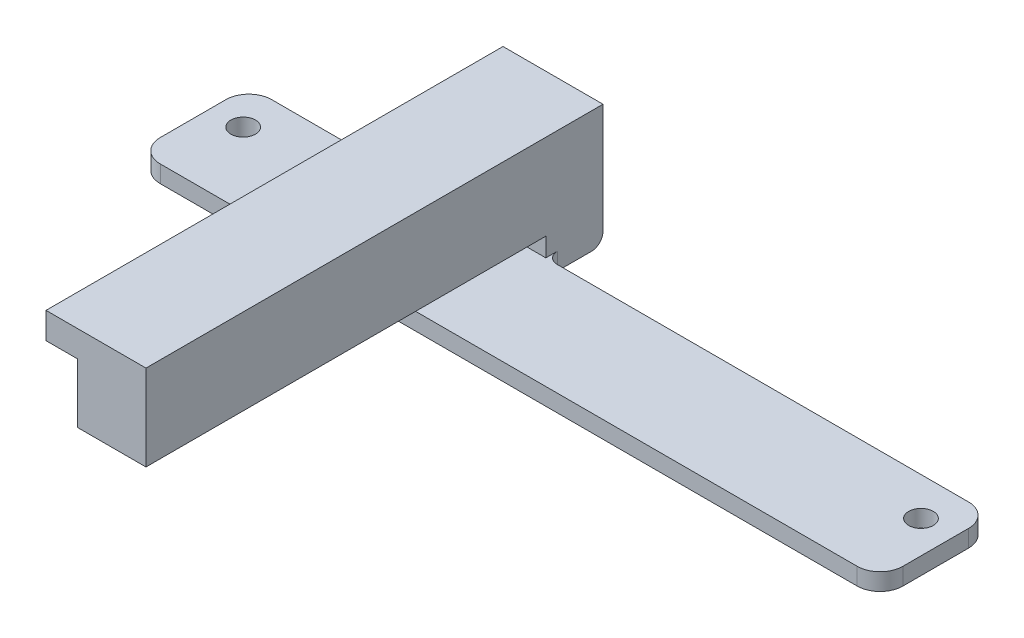
SolidWorks part; units mm, degrees
ref_plane "Front Plane" through (0, 0, 0) normal (0, 0, 1) x (1, 0, 0)
ref_plane "Top Plane" through (0, 0, 0) normal (0, 1, 0) x (1, 0, 0)
ref_plane "Right Plane" through (0, 0, 0) normal (1, 0, 0) x (0, 0, -1)
sketch "Sketch1" plane through (0, 0, 0) normal (0, 1, 0) x (1, 0, 0)
  line L1 (-65, -9.75) -> (65, -9.75)
  line L2 (-65, -9.75) -> (-65, 9.75)
  line L3 (-65, 9.75) -> (65, 9.75)
  line L4 (65, -9.75) -> (65, 9.75)
  line L5 (-65, -9.75) -> (65, 9.75) construction
  line L6 (-65, 9.75) -> (65, -9.75) construction
  point P0 (0, 0)
  dimension "D1" = 19.5
  dimension "D2" = 130
extrude "Boss-Extrude1" add sketch "Sketch1" along normal blind 3
fillet "Fillet1" radius 4 4 edges at (65, 1.5, 9.75) (-65, 1.5, 9.75) (-65, 1.5, -9.75) (65, 1.5, -9.75)
sketch "Sketch2" plane through (0, 3, 0) normal (0, 1, 0) x (1, 0, 0)
  line L0 (61, 9.75) -> (-61, 9.75) construction
  line L1 (-30.5, 9.75) -> (-13, 9.75)
  line L2 (-30.5, 9.75) -> (-30.5, 19.75)
  line L3 (-30.5, 19.75) -> (-13, 19.75)
  line L4 (-13, 9.75) -> (-13, 19.75)
  line L5 (65, -5.75) -> (65, 5.75) construction
  dimension "D1" = 78
  dimension "D2" = 95.5
  dimension "D3" = 10
extrude "Boss-Extrude2" add sketch "Sketch2" along normal blind 18.3 and the other way up to surface (3 mm away) other way up to face at (0, 0, 0)
sketch "Sketch3" plane through (0, 0, -9.75) normal (0, 0, 1) x (1, 0, 0)
  line L9 (-30.5, 3) -> (-30.5, 21.3) construction
  line L10 (-30.5, 16.7) -> (-25, 16.7)
  line L11 (-30.5, 16.7) -> (-30.5, 6.3)
  line L12 (-30.5, 6.3) -> (-25, 6.3)
  line L13 (-25, 16.7) -> (-25, 6.3)
  line L19 (-61, 3) -> (61, 3) construction
  dimension "D1" = 5.5
  dimension "D2" = 10.4
  dimension "D3" = 3.3
fillet "Fillet2" radius 2 2 edges at (-21.75, 0, -19.75) (-13, 1.5, -9.75)
sketch "Sketch4" plane through (0, 0, 0) normal (0, -1, 0) x (1, 0, 0)
  line L0 (0, 9.75) -> (0, -9.75) construction
  line L1 (-61, 9.75) -> (61, 9.75) construction
  line L2 (61, -9.75) -> (-11, -9.75) construction
  line L3 (-30.5, -9.75) -> (-61, -9.75) construction
  circle A0 centre (-59.325, -3.09) radius 2.15
  circle A1 centre (59.325, -3.09) radius 2.15
  dimension "D1" = 118.65
  dimension "D3" = 4.3
  dimension "D2" = 6.66
extrude "Cut-Extrude2" cut sketch "Sketch4" against normal up to surface (3 mm away) up to face at (-5.6595, 3, -3.3821)
extrude "Cut-Extrude3" cut sketch "Sketch3" against normal up to surface (10 mm away) up to face at (-21.75, 11.65, -19.75)
sketch "Sketch6" plane through (0, 0, -9.75) normal (0, 0, 1) x (1, 0, 0)
  line L0 (-30.5, 21.3) -> (-13, 21.3)
  line L1 (-13, 21.3) -> (-13, 6.3)
  line L2 (-13, 3) -> (-13, 21.3) construction
  line L3 (-13, 6.3) -> (-25, 6.3)
  line L4 (-25, 6.3) -> (-25, 16.7)
  line L5 (-25, 16.7) -> (-30.5, 16.7)
  line L6 (-30.5, 16.7) -> (-30.5, 21.3)
extrude "Boss-Extrude4" add sketch "Sketch6" along normal blind 70
